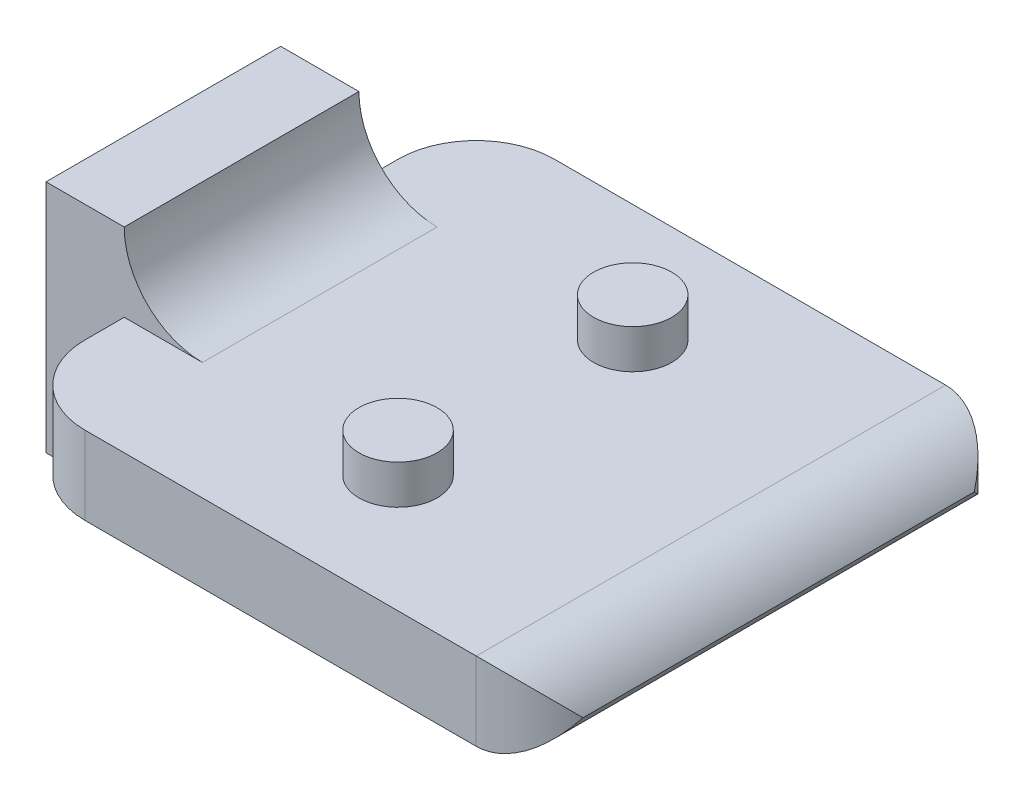
SolidWorks part; units mm, degrees
ref_plane "Front Plane" through (0, 0, 0) normal (0, 0, 1) x (1, 0, 0)
ref_plane "Top Plane" through (0, 0, 0) normal (0, 1, 0) x (1, 0, 0)
ref_plane "Right Plane" through (0, 0, 0) normal (1, 0, 0) x (0, 0, -1)
sketch "Sketch1" plane through (0, 0, 0) normal (0, 1, 0) x (1, 0, 0)
  line L1 (-35, 30) -> (35, 30)
  line L2 (-35, 30) -> (-35, -30)
  line L3 (-35, -30) -> (35, -30)
  line L4 (35, 30) -> (35, -30)
  line L5 (-35, 30) -> (35, -30) construction
  line L6 (-35, -30) -> (35, 30) construction
  line L7 (-35, 15) -> (-45, 15)
  line L8 (-35, 15) -> (-35, -15)
  line L9 (-35, -15) -> (-45, -15)
  line L10 (-45, 15) -> (-45, -15)
  point P0 (0, 0)
  dimension "D1" = 60
  dimension "D2" = 30
  dimension "D3" = 15
  dimension "D4" = 10
  dimension "D5" = 70
extrude "Boss-Extrude1" add sketch "Sketch1" along normal blind 10 contours L7 L10 L9 L2 | L4 L1 L2 L3 region at (0, 0, 0) region at (-40, 0, 0)
sketch "Sketch2" plane through (0, 10, 0) normal (0, 1, 0) x (1, 0, 0)
  line L1 (-35, 15) -> (-45, 15)
  line L2 (-35, 15) -> (-35, -15)
  line L3 (-35, -15) -> (-45, -15)
  line L4 (-45, 15) -> (-45, -15)
extrude "Boss-Extrude2" add sketch "Sketch2" along normal blind 10 and the other way blind 20
fillet "Fillet1" radius 10 8 edges at (35, 5, 30) (35, 10, 0) (35, 5, -30) (35, 0, 0) (-35, 0, 0) (-35, 10, 0) (-35, 5, -30) (-35, 5, 30)
sketch "Sketch3" plane through (0, 10, 0) normal (0, 1, 0) x (1, 0, 0)
  circle A0 centre (0, 15) radius 5
  circle A1 centre (0, -15) radius 5
  dimension "D1" = 10
  dimension "D2" = 10
  dimension "D3" = 15
  dimension "D4" = 15
extrude "Boss-Extrude3" add sketch "Sketch3" along normal blind 5
sketch "Sketch4" plane through (-45, 0, 0) normal (-1, 0, 0) x (0, 0, 1)
  line L1 (-8.139, 8.1997) -> (8.139, 8.1997)
  line L2 (-8.139, 8.1997) -> (-8.139, 1.8003)
  line L3 (-8.139, 1.8003) -> (8.139, 1.8003)
  line L4 (8.139, 8.1997) -> (8.139, 1.8003)
  line L5 (-8.139, 8.1997) -> (8.139, 1.8003) construction
  line L6 (-8.139, 1.8003) -> (8.139, 8.1997) construction
  point P0 (0, 5)
extrude "Cut-Extrude1" cut sketch "Sketch4" against normal blind 5
